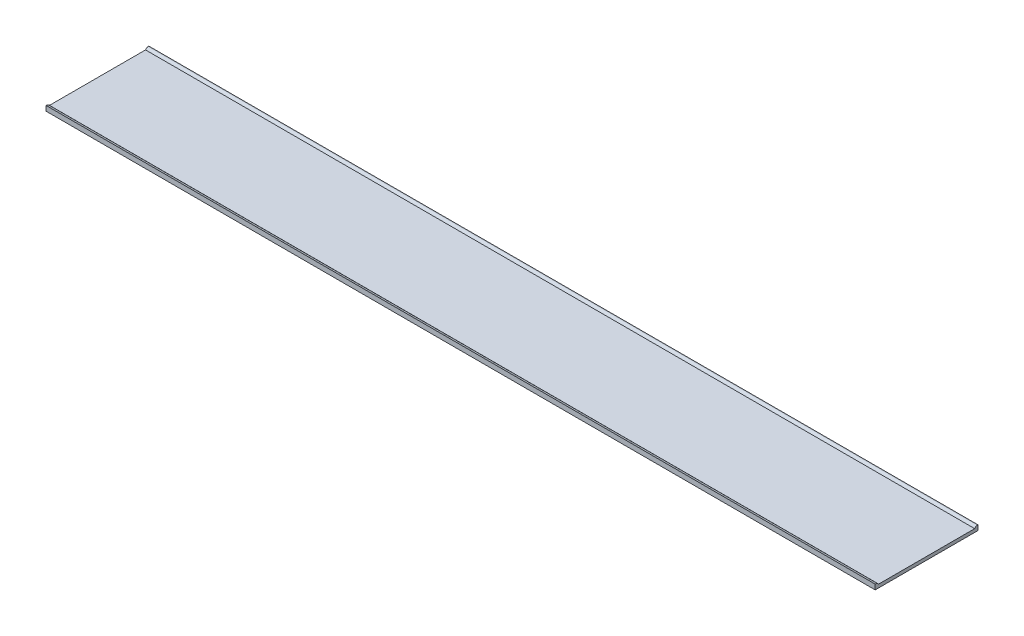
SolidWorks part; units mm, degrees
ref_plane "Alzado" through (0, 0, 0) normal (0, 0, 1) x (1, 0, 0)
ref_plane "Planta" through (0, 0, 0) normal (0, 1, 0) x (1, 0, 0)
ref_plane "Vista lateral" through (0, 0, 0) normal (1, 0, 0) x (0, 0, -1)
sketch "Croquis1" plane through (0, 0, 0) normal (0, 1, 0) x (1, 0, 0)
  line L1 (-250, -29) -> (250, -29)
  line L2 (-250, -29) -> (-250, 29)
  line L3 (-250, 29) -> (250, 29)
  line L4 (250, -29) -> (250, 29)
  line L5 (-250, -29) -> (250, 29) construction
  line L6 (-250, 29) -> (250, -29) construction
  point P0 (0, 0)
  dimension "D1" = 58
  dimension "D2" = 500
extrude "Saliente-Extruir1" add sketch "Croquis1" along normal blind 2
sketch "Croquis4" plane through (0, 0, 0) normal (0, 1, 0) x (1, 0, 0)
  line L0 (-294.201, 0) -> (332.7802, 0) construction
  line L1 (-250, 31) -> (250, 31)
  line L2 (-250, 31) -> (-250, 29)
  line L3 (-250, 29) -> (250, 29)
  line L4 (250, 31) -> (250, 29)
  line L5 (-250, 31) -> (250, 29) construction
  line L6 (-250, 29) -> (250, 31) construction
  line L7 (-250, -29) -> (250, -29)
  line L8 (250, -31) -> (250, -29)
  line L9 (-250, -31) -> (250, -31)
  line L10 (-250, -31) -> (-250, -29)
  point P0 (0, 30)
  dimension "D1" = 500
  dimension "D2" = 2
extrude "Saliente-Extruir2" add sketch "Croquis4" along normal blind 3
fillet "Redondeo1" radius 2 2 edges at (0, 3, -29) (0, 3, 29)
